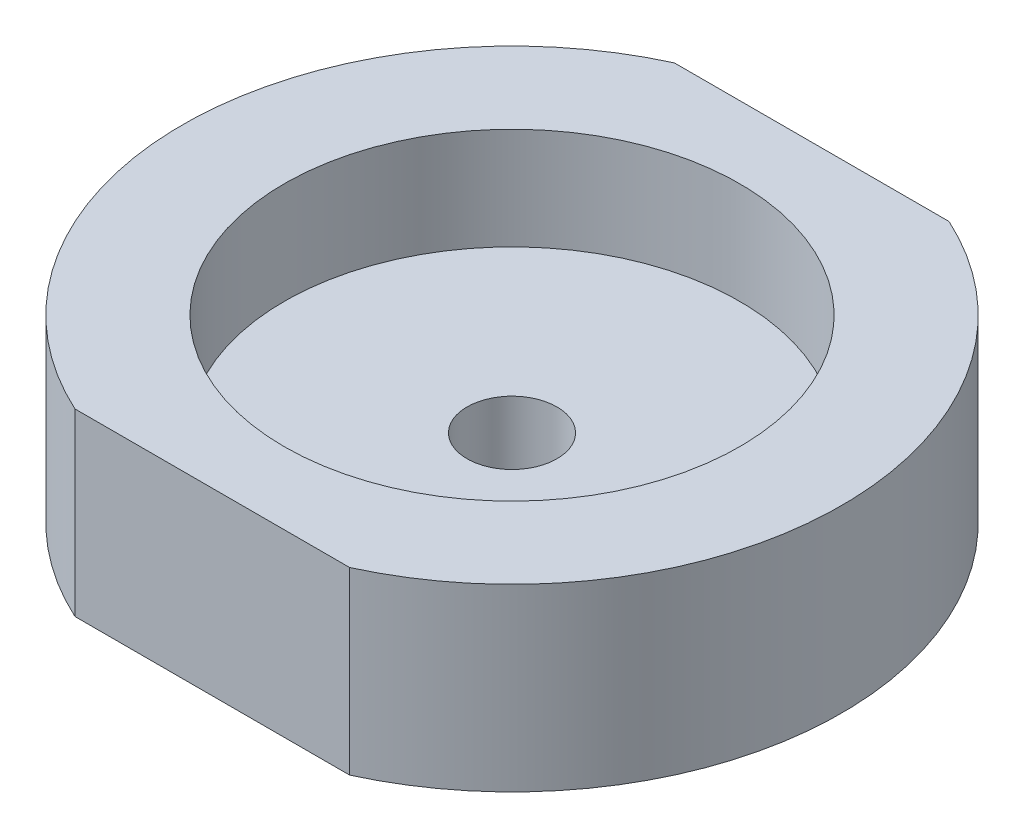
SolidWorks part; units mm, degrees
ref_plane "前视基准面" through (0, 0, 0) normal (0, 0, 1) x (1, 0, 0)
ref_plane "上视基准面" through (0, 0, 0) normal (0, 1, 0) x (1, 0, 0)
ref_plane "右视基准面" through (0, 0, 0) normal (1, 0, 0) x (0, 0, -1)
other "Configuration Table"
sketch "草图1" plane through (0, 0, 0) normal (0, 1, 0) x (1, 0, 0)
  line L1 (-6.1571, -5) -> (6.1571, -5)
  line L2 (-6.1571, -5) -> (-6.1571, 5)
  line L3 (-6.1571, 5) -> (6.1571, 5)
  line L4 (6.1571, -5) -> (6.1571, 5)
  line L5 (-6.1571, -5) -> (6.1571, 5) construction
  line L6 (-6.1571, 5) -> (6.1571, -5) construction
  circle A0 centre (0, 0) radius 5
  circle A1 centre (0, 0) radius 5.5
  dimension "D1" = 10
  dimension "D2" = 11
extrude "凸台-拉伸1" add sketch "草图1" along normal blind 3 contours L3 A1 L1 A0 | A0 | L1 A1 L3 A0 region at (-5.3859, 0, 0) region at (3.6162, 0, 3.6162) region at (0, 0, 0)
sketch "草图2" plane through (0, 3, 0) normal (0, 1, 0) x (1, 0, 0)
  circle A0 centre (0, 0) radius 3.8
  dimension "D1" = 7.6
extrude "切除-拉伸1" cut sketch "草图2" against normal blind 1.7
sketch "草图3" plane through (0, 1.3, 0) normal (0, -1, 0) x (-1, 0, 0)
  circle A0 centre (0, 0) radius 0.75
  dimension "D1" = 1.5
extrude "切除-拉伸2" cut sketch "草图3" along normal through all
